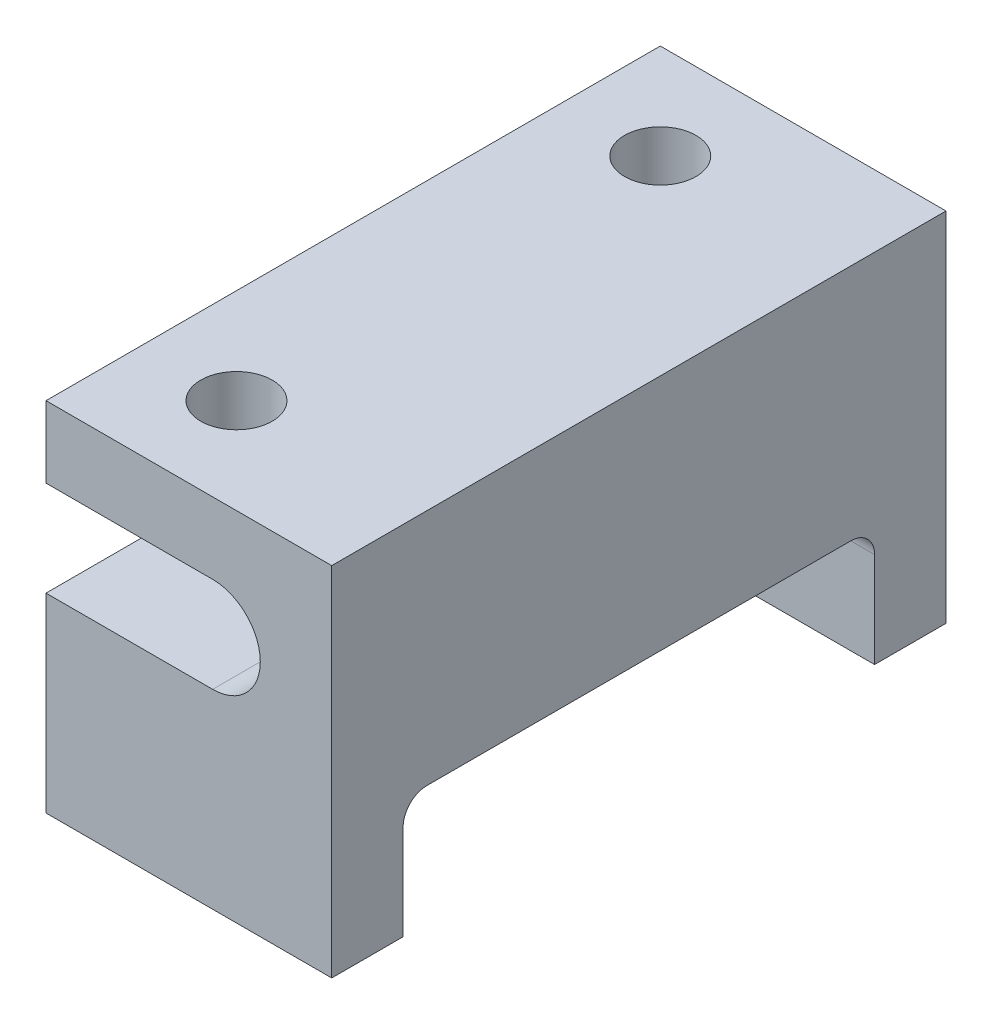
SolidWorks part; units mm, degrees
ref_plane "Front Plane" through (0, 0, 0) normal (0, 0, 1) x (1, 0, 0)
ref_plane "Top Plane" through (0, 0, 0) normal (0, 1, 0) x (1, 0, 0)
ref_plane "Right Plane" through (0, 0, 0) normal (1, 0, 0) x (0, 0, -1)
sketch "Sketch1" plane through (0, 0, 0) normal (0, 0, 1) x (1, 0, 0)
  line L0 (0, 0) -> (9, 0)
  line L1 (9, 0) -> (9, -4)
  line L2 (9, -4) -> (0, -4)
  line L3 (0, -4) -> (0, -7)
  line L4 (0, -7) -> (12, -7)
  line L5 (12, -7) -> (12, 3)
  line L6 (12, 3) -> (0, 3)
  line L7 (0, 3) -> (0, 0)
  dimension "D1" = 3
  dimension "D2" = 3
  dimension "D3" = 3
  dimension "D4" = 4
  dimension "D5" = 9
extrude "Boss-Extrude1" add sketch "Sketch1" along normal mid plane 25.8
sketch "Sketch2" plane through (12, 0, 0) normal (1, 0, 0) x (0, 0, -1)
  line L0 (-12.9, -7) -> (-12.9, -12)
  line L1 (-12.9, -12) -> (-9.9, -12)
  line L2 (-9.9, -12) -> (-9.9, -7)
  line L3 (-12.9, -7) -> (12.9, -7) construction
  line L4 (-9.9, -7) -> (-12.9, -7)
  line L5 (12.9, -7) -> (12.9, -12)
  line L6 (12.9, -12) -> (9.9, -12)
  line L7 (9.9, -12) -> (9.9, -7)
  line L8 (9.9, -7) -> (12.9, -7)
  line L9 (-9.9, -12) -> (9.9, -12) construction
  dimension "D1" = 3
  dimension "D2" = 3
  dimension "D3" = 5
extrude "Boss-Extrude2" add sketch "Sketch2" against normal through all
sketch "Sketch3" plane through (0, -7, 0) normal (0, -1, 0) x (1, 0, 0)
  line L0 (0, 0) -> (12, 0) construction
  line L1 (0, 9.9) -> (0, -9.9) construction
  line L2 (12, 9.9) -> (12, -9.9) construction
  circle A0 centre (4, 0) radius 1.8
  dimension "D1" = 3.6
  dimension "D2" = 4
extrude "Cut-Extrude1" cut sketch "Sketch3" against normal blind 5
fillet "Fillet1" radius 2 2 edges at (9, -4, 0) (9, 0, 0)
fillet "Fillet2" radius 1 2 edges at (6, -7, -9.9) (6, -7, 9.9)
sketch "Sketch4" plane through (0, 3, 0) normal (0, 1, 0) x (1, 0, 0)
  line L0 (4, 8.9) -> (4, -8.9) construction
  line L1 (0, -12.9) -> (0, 12.9) construction
  line L2 (12, 12.9) -> (0, 12.9) construction
  line L3 (12, -12.9) -> (0, -12.9) construction
  circle A0 centre (4, 8.9) radius 1.5
  circle A1 centre (4, -8.9) radius 1.5
  dimension "D2" = 3
  dimension "D3" = 3
  dimension "D1" = 4
  dimension "D4" = 4
  dimension "D5" = 4
extrude "Cut-Extrude2" cut sketch "Sketch4" against normal blind 3
